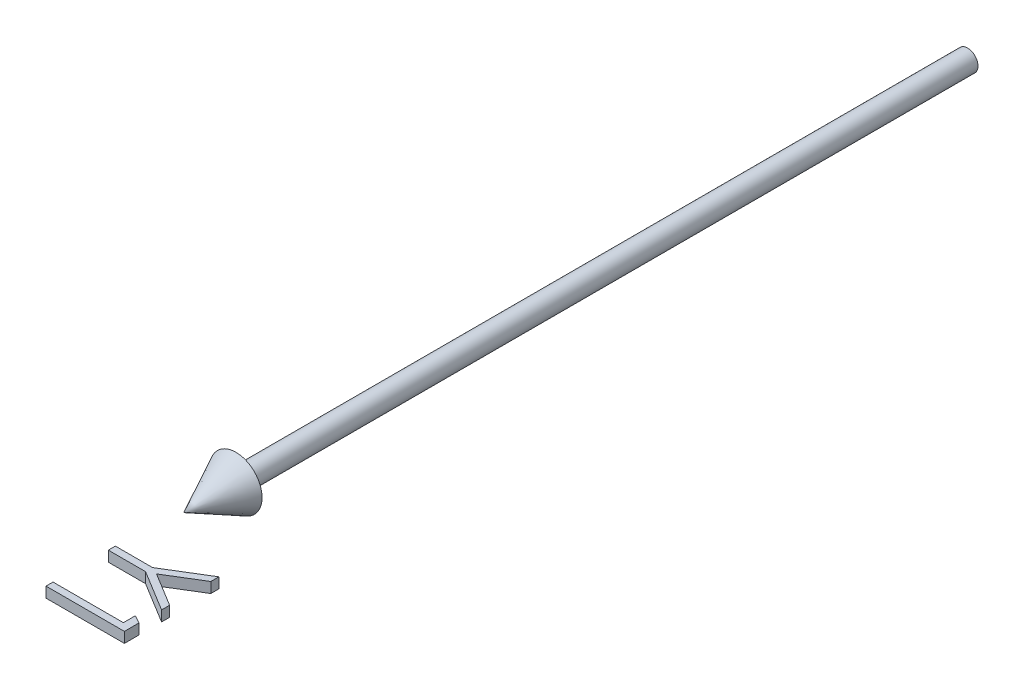
SolidWorks part; units mm, degrees
ref_plane "Front Plane" through (0, 0, 0) normal (0, 0, 1) x (1, 0, 0)
ref_plane "Top Plane" through (0, 0, 0) normal (0, 1, 0) x (1, 0, 0)
ref_plane "Right Plane" through (0, 0, 0) normal (1, 0, 0) x (0, 0, -1)
sketch "Sketch2" plane through (0, 0, 0) normal (0, 1, 0) x (1, 0, 0)
  line L0 (0, 41.95) -> (0, -114.4521) construction
  line L1 (-36.8894, 0) -> (41.4965, 0) construction
  line L2 (0, -150) -> (5, -140)
  line L3 (5, -140) -> (2, -140)
  line L4 (2, -140) -> (2, 0)
  line L5 (2, 0) -> (0, 0)
  line L6 (0, 0) -> (0, -150)
  dimension "D1" = 150
  dimension "D2" = 2
  dimension "D3" = 10
  dimension "D4" = 5
revolve "Revolve1" add sketch "Sketch2" angle 360 about L0
sketch "Sketch3" plane through (0, 0, 0) normal (0, 1, 0) x (1, 0, 0)
  line L0 (0, -157.5) -> (0, -303.5812) construction
  line L1 (-35.6006, 0) -> (44.8667, 0) construction
  text T0 "Y1" font "Century Gothic" height 15
  dimension "D1" = 157.5
extrude "Boss-Extrude1" add sketch "Sketch3" against normal blind 1 and the other way blind 1 separate body
equation "\"D1@Sketch2\"=\"frame_arrow_length\""
equation "\"D2@Sketch2\"=\"frame_arrow_odA\"/2"
equation "\"D4@Sketch2\"=\"frame_arrow_head_od\""
equation "\"D3@Sketch2\"=\"frame_arrow_head_length\""
equation "\"frame_arrow_length\"=150"
equation "\"frame_arrow_head_length\"=10"
equation "\"frame_arrow_head_od\"=5"
equation "\"frame_arrow_odA\"=4"
equation "\"D1@Sketch3\"=\"frame_arrow_length\"*1.05"
